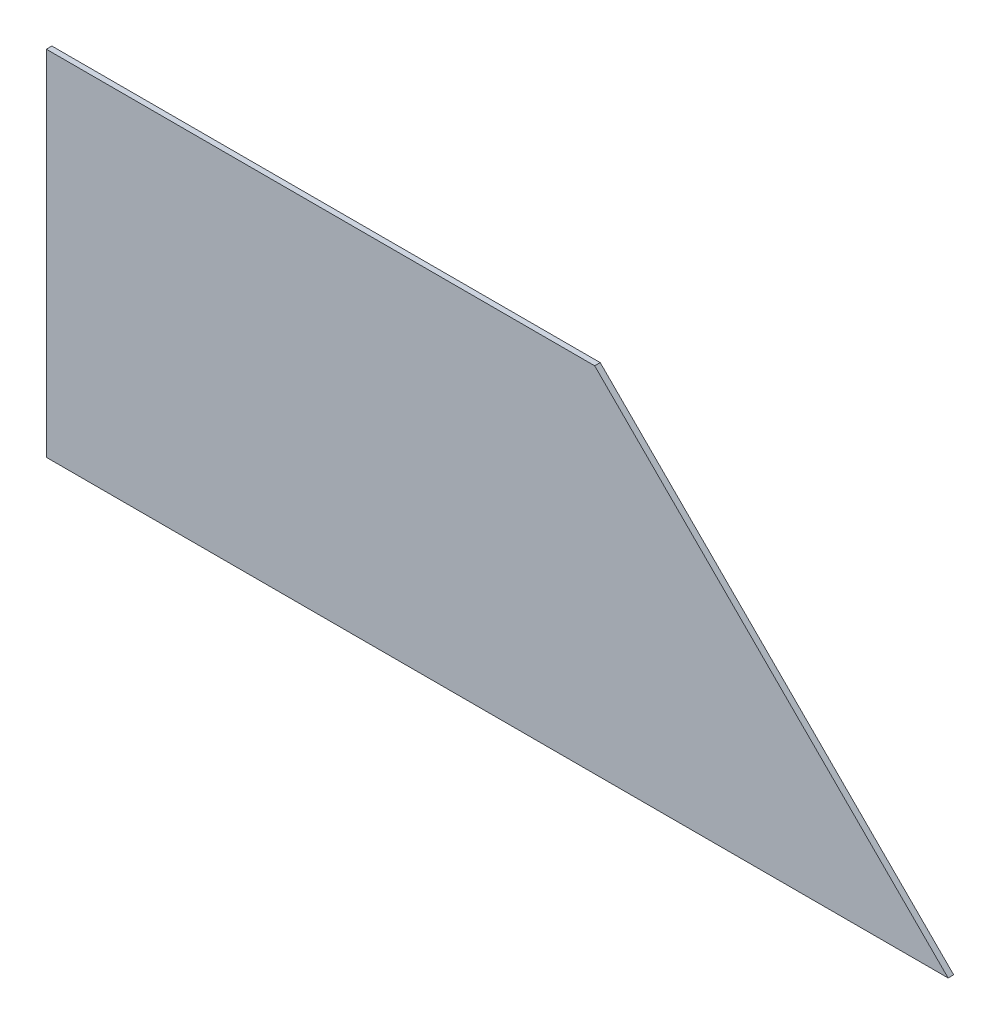
SolidWorks part; units mm, degrees
ref_plane "Front Plane" through (0, 0, 0) normal (0, 0, 1) x (1, 0, 0)
ref_plane "Top Plane" through (0, 0, 0) normal (0, 1, 0) x (1, 0, 0)
ref_plane "Right Plane" through (0, 0, 0) normal (1, 0, 0) x (0, 0, -1)
sketch "Sketch1" plane through (0, 0, 0) normal (0, 0, 1) x (1, 0, 0)
  line L0 (315.214, 203.2) -> (518.414, 0)
  line L1 (0, 0) -> (127, 0)
  line L2 (0, 0) -> (0, 203.2)
  line L3 (0, 203.2) -> (315.214, 203.2)
  line L5 (518.414, 0) -> (127, 0)
  dimension "D1" = 315.214
  dimension "D2" = 203.2
  dimension "D3" = 45
extrude "Boss-Extrude1" add sketch "Sketch1" along normal blind 3.175
